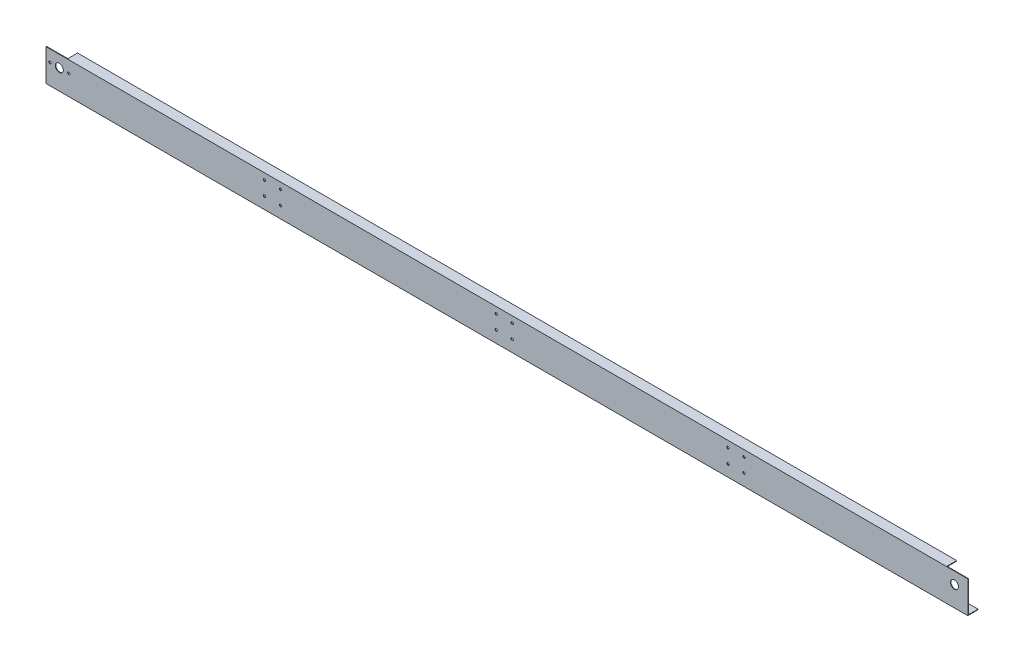
SolidWorks part; units mm, degrees
material "Galvanized Steel"
ref_plane "Front Plane" through (0, 0, 0) normal (0, 0, 1) x (1, 0, 0)
ref_plane "Top Plane" through (0, 0, 0) normal (0, 1, 0) x (1, 0, 0)
ref_plane "Right Plane" through (0, 0, 0) normal (1, 0, 0) x (0, 0, -1)
sketch "Sketch1" plane through (0, 0, 0) normal (1, 0, 0) x (0, 0, -1)
  line L0 (0, 0) -> (0, 127)
  line L1 (0, 127) -> (48.768, 127)
  line L4 (2.54, 2.54) -> (2.54, 124.46)
  line L5 (2.54, 124.46) -> (48.768, 124.46)
  line L6 (48.768, 127) -> (48.768, 124.46)
  line L8 (0, 0) -> (39.0507, 0) construction
  line L9 (2.54, 2.54) -> (39.0507, 2.54) construction
  line L10 (0, 0) -> (0, -25.4)
  line L11 (0, -25.4) -> (48.768, -25.4)
  line L12 (48.768, -25.4) -> (48.768, -22.86)
  line L13 (48.768, -22.86) -> (2.54, -22.86)
  line L14 (2.54, -22.86) -> (2.54, 2.54)
  dimension "D1" = 127
  dimension "D2" = 48.768
  dimension "D4" = 25.4
  dimension "D5" = 2.54
  dimension "D3" = 2.54
extrude "Boss-Extrude1" add sketch "Sketch1" along normal blind 4394.2
sketch "Sketch2" plane through (0, 0, -2.54) normal (0, 0, -1) x (-1, 0, 0)
  line L0 (-4394.2, 127) -> (0, 127) construction
  line L1 (-4394.2, -22.86) -> (-4394.2, 124.46) construction
  line L2 (0, -22.86) -> (0, 124.46) construction
  circle A0 centre (-4330.7, 71.12) radius 19.05
  circle A1 centre (-63.5, 71.12) radius 19.05
  circle A2 centre (-18.4547, 71.12) radius 5.5562
  circle A3 centre (-108.5453, 71.12) radius 5.5563
  dimension "D1" = 38.1
  dimension "D4" = 38.1
  dimension "D7" = 11.1125
  dimension "D8" = 11.1125
  dimension "D2" = 55.88
  dimension "D3" = 63.5
  dimension "D5" = 55.88
  dimension "D6" = 63.5
  dimension "D9" = 45.0453
  dimension "D10" = 45.0453
extrude "Cut-Extrude1" cut sketch "Sketch2" against normal up to next
sketch "Sketch3" plane through (0, 0, -2.54) normal (0, 0, -1) x (-1, 0, 0)
  line L19 (-4394.2, 124.46) -> (0, 124.46) construction
  line L20 (-4394.2, 127) -> (-4292.6, 127)
  line L21 (-4394.2, 127) -> (-4394.2, 124.46)
  line L22 (-4394.2, 124.46) -> (-4292.6, 124.46)
  line L23 (-4292.6, 127) -> (-4292.6, 124.46)
  line L25 (0, 127) -> (-101.6, 127)
  line L26 (0, 127) -> (0, 124.46)
  line L27 (0, 124.46) -> (-101.6, 124.46)
  line L28 (-101.6, 127) -> (-101.6, 124.46)
  dimension "D1" = 101.6
  dimension "D2" = 101.6
extrude "Cut-Extrude4" cut sketch "Sketch3" along normal up to next
sketch "Sketch4" plane through (0, 0, -2.54) normal (0, 0, -1) x (-1, 0, 0)
  circle A0 centre (-3327.4, 96.774) radius 5.5563
  circle A1 centre (-3251.2, 96.774) radius 5.5563
  circle A2 centre (-3251.2, 30.226) radius 5.5563
  circle A3 centre (-3327.4, 30.226) radius 5.5563
  circle A4 centre (-2222.5, 96.774) radius 5.5562
  circle A5 centre (-2146.3, 96.774) radius 5.5563
  circle A6 centre (-2146.3, 30.226) radius 5.5563
  circle A7 centre (-2222.5, 30.226) radius 5.5563
  circle A8 centre (-1117.6, 96.774) radius 5.5563
  circle A9 centre (-1041.4, 96.774) radius 5.5563
  circle A10 centre (-1041.4, 30.226) radius 5.5563
  circle A11 centre (-1117.6, 30.226) radius 5.5563
  dimension "D3" = 11.1125
  dimension "D1" = 76.2
  dimension "D2" = 66.548
  dimension "D6" = 3
extrude "Cut-Extrude5" cut sketch "Sketch4" against normal up to next
